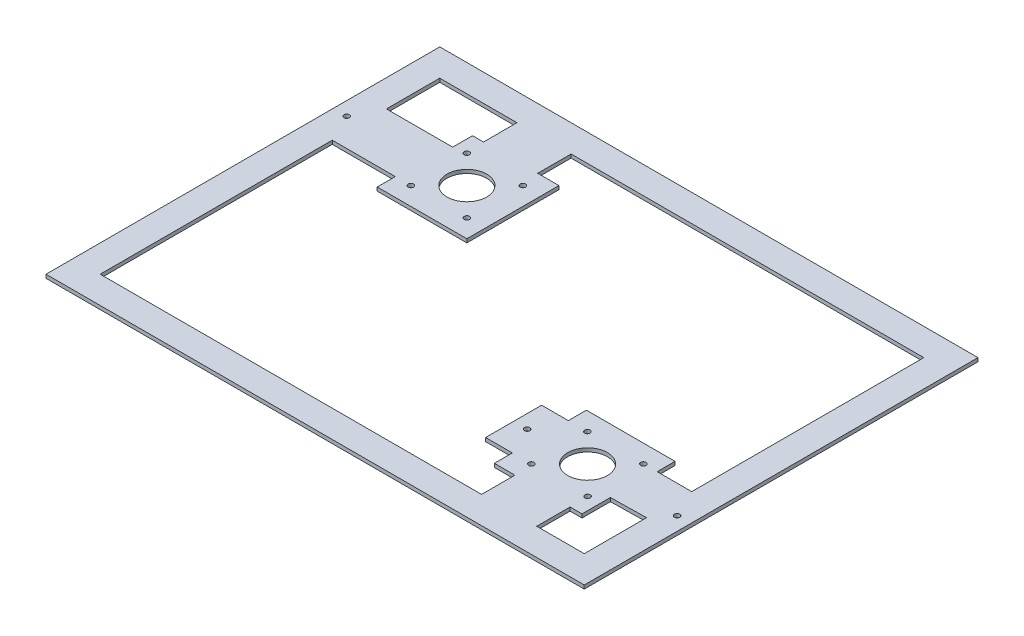
SolidWorks part; units mm, degrees
ref_plane "Front Plane" through (0, 0, 0) normal (0, 0, 1) x (1, 0, 0)
ref_plane "Top Plane" through (0, 0, 0) normal (0, 1, 0) x (1, 0, 0)
ref_plane "Right Plane" through (0, 0, 0) normal (1, 0, 0) x (0, 0, -1)
sketch "Sketch1" plane through (0, 0, 0) normal (1, 0, 0) x (0, 0, -1)
  line L0 (-26.6783, 0) -> (191.3217, 0)
  line L1 (119.9, 0) -> (-119.9, 0) construction
  line L2 (-26.6783, 0) -> (-26.6783, 2)
  line L3 (191.3217, 0) -> (191.3217, 2)
  line L4 (191.3217, 2) -> (-26.6783, 2)
  dimension "D1" = 218
  dimension "D2" = 2
extrude "Boss-Extrude1" add sketch "Sketch1" along normal blind 298 contours L4 L2 L0 L3
sketch "Sketch2" plane through (0, 2, 0) normal (0, 1, 0) x (1, 0, 0)
  line L0 (0, -1.1) -> (0, 1.1) construction
  line L5 (298, 191.3217) -> (0, 191.3217) construction
  line L6 (15, 176.3217) -> (57.7212, 176.3217)
  line L7 (128.5445, 82.3217) -> (183.6204, 82.3217) construction
  line L18 (74, 132.3217) -> (85, 132.3217) construction
  line L20 (149, 244.2227) -> (149, 176.3217) construction
  line L23 (15, 176.3217) -> (15, 159.517)
  line L24 (298, -26.6783) -> (0, -26.6783) construction
  line L27 (85, 132.3217) -> (-63.8787, 132.3217) construction
  line L28 (149, -11.6783) -> (104.4712, -11.6783)
  line L29 (99.5, 106.8217) -> (99.5, 157.8217)
  line L30 (101.2006, 176.3217) -> (149, 176.3217)
  line L31 (51.6521, 157.8217) -> (57.7212, 157.8217)
  line L32 (104.4712, -11.6783) -> (15, -11.6783)
  line L34 (99.5, 106.8217) -> (49.8733, 106.8217)
  line L35 (15, -11.6783) -> (15, 89.9418)
  line L36 (57.7212, 176.3217) -> (57.7212, 157.8217)
  line L37 (99.5, 157.8217) -> (87.7212, 157.8217)
  line L39 (101.2006, 176.3217) -> (87.7212, 176.3217)
  line L40 (87.7212, 157.8217) -> (87.7212, 176.3217)
  line L42 (15, 89.9418) -> (15, 116.8217)
  line L43 (15, 116.8217) -> (49.8733, 116.8217)
  line L44 (49.8733, 106.8217) -> (49.8733, 116.8217)
  line L46 (15, 159.517) -> (15, 146.8217)
  line L47 (15, 146.8217) -> (51.6521, 146.8217)
  line L48 (51.6521, 157.8217) -> (51.6521, 146.8217)
  line L49 (283, 47.8217) -> (283, 176.3217)
  line L50 (283, 176.3217) -> (149, 176.3217)
  line L51 (226.1545, -11.6783) -> (149, -11.6783)
  line L52 (149, -11.6783) -> (149, -99.356) construction
  line L62 (214.9875, 235.2083) -> (214.9875, 57.7194) construction
  line L63 (283, 47.8217) -> (263.8762, 47.8217)
  line L64 (283, -11.6783) -> (283, 10.1264)
  line L65 (283, 10.1264) -> (283, 22.8217)
  line L66 (283, 22.8217) -> (263.3054, 22.4886)
  line L67 (263.3054, 6.7817) -> (263.3054, 22.4886)
  line L68 (263.3054, 6.7817) -> (256.6954, 6.7817)
  line L69 (256.6954, -11.6783) -> (256.6954, 6.7817)
  line L70 (283, -11.6783) -> (256.6954, -11.6783)
  line L71 (214.7904, 57.7194) -> (214.7904, 47.7194)
  line L72 (214.7904, 57.7194) -> (263.8762, 57.7194)
  line L73 (214.7904, 6.7771) -> (226.1545, 6.7771)
  line L75 (226.1545, 6.7771) -> (226.1545, -11.6783)
  line L76 (263.8762, 57.7194) -> (263.8762, 47.8217)
  line L77 (214.7904, 16.7194) -> (214.7904, 6.7771)
  line L78 (214.7904, 47.7194) -> (199.9904, 47.7194)
  line L80 (214.7904, 16.7194) -> (199.9904, 16.7194)
  line L81 (199.9904, 47.7194) -> (199.9904, 16.7194)
  line L82 (214.9875, 6.7771) -> (214.9875, -106.0424) construction
  line L83 (298, 191.3217) -> (298, -26.6783) construction
  circle A0 centre (74, 132.3217) radius 11
  circle A4 centre (89.5, 116.8217) radius 1.5
  circle A5 centre (58.5, 116.8217) radius 1.5
  circle A6 centre (89.5, 147.8217) radius 1.5
  circle A7 centre (58.5, 147.8217) radius 1.5
  circle A13 centre (256.3313, 47.7194) radius 1.5
  circle A14 centre (256.4575, 16.7194) radius 1.5
  circle A15 centre (225.3313, 16.7194) radius 1.5
  circle A16 centre (225.3313, 47.7194) radius 1.5
  circle A17 centre (240.9575, 32.2194) radius 11
  circle A18 centre (290.5, 32.2194) radius 1.5
  circle A19 centre (7.5, 132.3217) radius 1.5
  circle A20 centre (207.4904, 32.2194) radius 1.5
  point P52 (57.7212, 167.0717)
  dimension "D9" = 22
  dimension "D10" = 3
  dimension "D11" = 3
  dimension "D31" = 3
  dimension "D32" = 3
  dimension "D37" = 3
  dimension "D2" = 50
  dimension "D3" = 150
  dimension "D4" = 109
  dimension "D5" = 15
  dimension "D6" = 15
  dimension "D7" = 30
  dimension "D8" = 31
  dimension "D12" = 31
  dimension "D13" = 15.5
  dimension "D14" = 15.5
  dimension "D15" = 149
  dimension "D16" = 30
  dimension "D17" = 15
  dimension "D18" = 15
  dimension "D19" = 10
  dimension "D20" = 10
  dimension "D21" = 10
  dimension "D22" = 10
  dimension "D23" = 10
  dimension "D24" = 15
  dimension "D25" = 7.5
  dimension "D26" = 15
  dimension "D27" = 15
  dimension "D28" = 18.46
  dimension "D29" = 34.6946
  dimension "D30" = 15
  dimension "D33" = 7.5
  dimension "D34" = 68.2096
  dimension "D35" = 14.8
  dimension "D36" = 7.5
extrude "Cut-Extrude1" cut sketch "Sketch2" against normal blind 10
